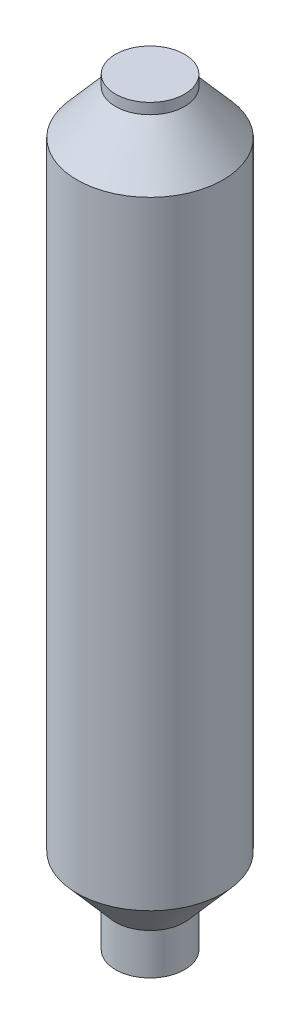
SolidWorks part; units mm, degrees
ref_plane "Front Plane" through (0, 0, 0) normal (0, 0, 1) x (1, 0, 0)
ref_plane "Top Plane" through (0, 0, 0) normal (0, 1, 0) x (1, 0, 0)
ref_plane "Right Plane" through (0, 0, 0) normal (1, 0, 0) x (0, 0, -1)
sketch "Sketch1" plane through (0, 0, 0) normal (0, 0, 1) x (1, 0, 0)
  line L0 (0, 0) -> (0, 70)
  line L1 (0, 70) -> (3.1888, 70)
  line L2 (3.1888, 70) -> (3.1888, 69.0094)
  line L3 (3.1888, 69.0094) -> (6.7437, 64.92)
  line L4 (6.7437, 64.92) -> (3.1888, 64.92) construction
  line L5 (6.7437, 64.92) -> (6.7437, 7.884)
  line L6 (6.7437, 7.884) -> (3.1888, 3.7946)
  line L7 (3.1888, 3.7946) -> (3.1888, 0)
  line L8 (3.1888, 0) -> (0, 0)
  line L9 (3.1888, 3.7946) -> (3.1888, 7.884) construction
  line L10 (3.1888, 7.884) -> (6.7437, 7.884) construction
  line L11 (3.1888, 69.0094) -> (3.1888, 64.92) construction
  point P10 (3.175, 3.8568)
  point P12 (3.175, 3.8148)
  point P13 (6.7437, 7.8849)
  point P14 (6.7437, 7.8849)
  point P15 (6.7437, 7.884)
  point P16 (0, 0)
  dimension "D1" = 70
  dimension "D2" = 41
  dimension "D3" = 3.1888
  dimension "D4" = 6.7437
  dimension "D5" = 41
  dimension "D6" = 4.0894
  dimension "D7" = 4.0894
  dimension "D8" = 5.08
  dimension "D9" = 6.7437
revolve "Revolve1" add sketch "Sketch1" angle 360 about L0
